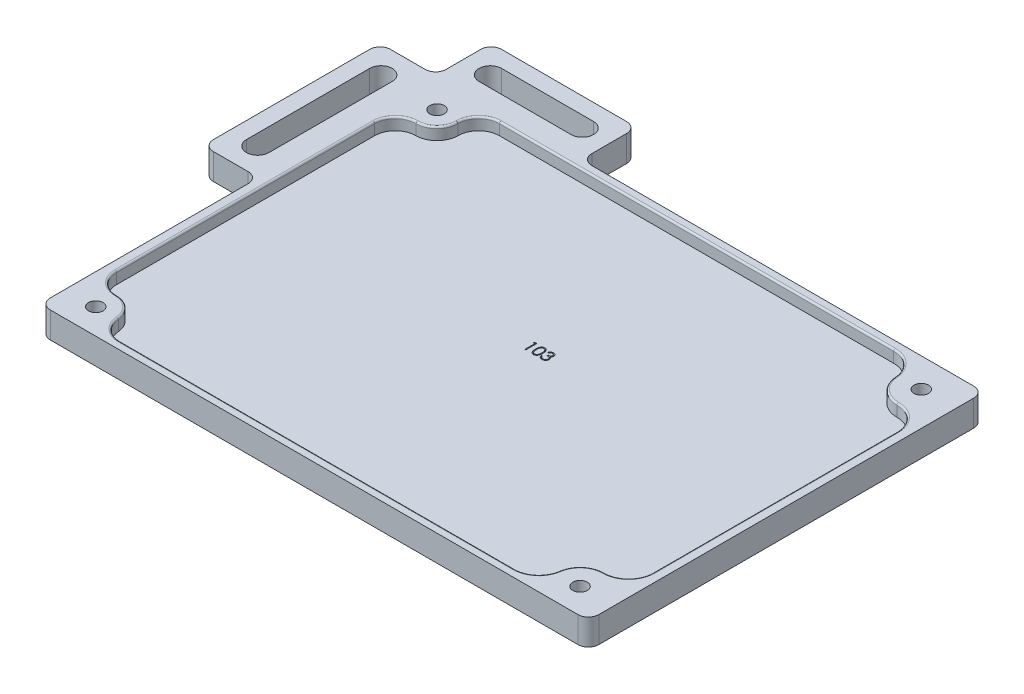
SolidWorks part; units mm, degrees
ref_plane "Front Plane" through (0, 0, 0) normal (0, 0, 1) x (1, 0, 0)
ref_plane "Top Plane" through (0, 0, 0) normal (0, 1, 0) x (1, 0, 0)
ref_plane "Right Plane" through (0, 0, 0) normal (1, 0, 0) x (0, 0, -1)
sketch "Sketch1" plane through (0, 0, 0) normal (0, 1, 0) x (1, 0, 0)
  line L1 (0, 0) -> (158, 0)
  line L2 (0, 0) -> (0, 114)
  line L3 (0, 114) -> (158, 114)
  line L4 (158, 0) -> (158, 114)
  line L5 (2.75, 2.35) -> (155.25, 2.35) construction
  line L6 (2.75, 2.35) -> (2.75, 111.65) construction
  line L7 (2.75, 111.65) -> (155.25, 111.65) construction
  line L8 (155.25, 2.35) -> (155.25, 111.65) construction
  circle A0 centre (8.75, 105.65) radius 2.09
  circle A1 centre (8.75, 7.35) radius 2.09
  circle A2 centre (148.25, 7.35) radius 2.09
  circle A3 centre (148.25, 105.65) radius 2.09
  point P20 (78.7625, 58.0063)
  dimension "D3" = 4.18
  dimension "D1" = 158
  dimension "D2" = 114
  dimension "D4" = 7
  dimension "D5" = 152.5
  dimension "D6" = 109.3
  dimension "D7" = 2.75
  dimension "D8" = 2.35
  dimension "D9" = 6
  dimension "D10" = 5
  dimension "D11" = 6
extrude "Boss-Extrude1" add sketch "Sketch1" along normal blind 7.5
extrude "Boss-Extrude2" add sketch "Sketch1<2>" along normal blind 2 from surface contours A0 | A3 | A1 | A2 region at (8.75, 0, -105.65) region at (148.25, 0, -105.65) starting at face at (148.25, 0, -5.26)
sketch "Sketch1<2>" plane through (0, 0, 0) normal (0, 1, 0) x (1, 0, 0) same geometry as "Sketch1"
sketch "Sketch2" plane through (0, 7.5, 0) normal (0, 1, 0) x (1, 0, 0)
  line L1 (20.7083, 2.35) -> (134.3936, 2.35)
  line L2 (2.75, 19.35) -> (2.75, 93.65)
  line L3 (20.75, 111.65) -> (134.2858, 111.65)
  line L4 (155.25, 21.35) -> (155.25, 91.65)
  arc A0 (8.75, 99.65) -> (14.75, 105.65) centre (8.75, 105.65) ccw
  arc A1 (14.7291, 7.85) -> (8.75, 13.35) centre (8.75, 7.35) ccw
  arc A2 (148.25, 14.35) -> (141.3218, 8.35) centre (148.25, 7.35) ccw
  arc A3 (141.2679, 105.15) -> (148.25, 98.65) centre (148.25, 105.65) ccw
  arc A4 (8.75, 99.65) -> (2.75, 93.65) centre (8.75, 93.65) ccw
  arc A5 (14.75, 105.65) -> (20.75, 111.65) centre (20.75, 105.65) cw
  arc A6 (8.75, 13.35) -> (2.75, 19.35) centre (8.75, 19.35) cw
  arc A7 (20.7083, 2.35) -> (14.7291, 7.85) centre (20.7083, 8.35) cw
  arc A8 (148.25, 14.35) -> (155.25, 21.35) centre (148.25, 21.35) ccw
  arc A9 (141.3218, 8.35) -> (134.3936, 2.35) centre (134.3936, 9.35) cw
  arc A10 (141.2679, 105.15) -> (134.2858, 111.65) centre (134.2858, 104.65) ccw
  arc A11 (148.25, 98.65) -> (155.25, 91.65) centre (148.25, 91.65) cw
  dimension "D1" = 6
  dimension "D2" = 6
  dimension "D3" = 6
  dimension "D4" = 7
  dimension "D5" = 7
  dimension "D6" = 7
extrude "Cut-Extrude1" cut sketch "Sketch2" against normal blind 3.5
sketch "Sketch3" plane through (0, 7.5, 0) normal (0, 1, 0) x (1, 0, 0)
  line L0 (-8, 70.75) -> (-8, 106.25) construction
  line L1 (0, 114) -> (-16, 114)
  line L2 (0, 114) -> (0, 63)
  line L3 (0, 63) -> (-16, 63)
  line L4 (-16, 114) -> (-16, 63)
  line L5 (-11.25, 70.75) -> (-11.25, 106.25)
  line L6 (-4.75, 70.75) -> (-4.75, 106.25)
  line L7 (7.75, 122) -> (34.25, 122) construction
  line L8 (0, 114) -> (42, 114)
  line L9 (0, 114) -> (0, 130)
  line L10 (0, 130) -> (42, 130)
  line L11 (42, 114) -> (42, 130)
  line L12 (7.75, 125.25) -> (34.25, 125.25)
  line L13 (7.75, 118.75) -> (34.25, 118.75)
  arc A0 (-11.25, 70.75) -> (-4.75, 70.75) centre (-8, 70.75) ccw
  arc A1 (-4.75, 106.25) -> (-11.25, 106.25) centre (-8, 106.25) ccw
  arc A2 (7.75, 125.25) -> (7.75, 118.75) centre (7.75, 122) ccw
  arc A3 (34.25, 118.75) -> (34.25, 125.25) centre (34.25, 122) ccw
  point P7 (-8, 88.5)
  point P17 (21, 122)
  point P22 (-8, 109.5)
  point P23 (-8, 67.5)
  point P24 (4.5, 122)
  point P25 (37.5, 122)
  line M35 (0, 114) -> (0, 0)
  line M38 (158, 114) -> (0, 114)
  dimension "D1" = 51
  dimension "D2" = 16
  dimension "D3" = 8
  dimension "D4" = 6.5
  dimension "D5" = 4.5
  dimension "D6" = 4.5
  dimension "D7" = 16
  dimension "D8" = 42
  dimension "D9" = 8
  dimension "D10" = 4.5
  dimension "D11" = 4.5
  dimension "D12" = 6.5
extrude "Boss-Extrude3" add sketch "Sketch3" against normal up to surface (7.5 mm away) contours L11 L10 L9 A3 L13 A2 L12 M38 | L1 L4 L3 A1 L6 A0 L5 M35 region at (-0.5345, 7.5, -88.5) region at (0.4494, 7.5, -122) up to face at (79, 0, -57)
fillet "Fillet1" radius 0.5 16 edges at (139.0555, 7.5, -109.7735) (143.4803, 7.5, -100.5265) (153.1997, 7.5, -96.5997) (155.25, 7.5, -56.5) (153.1997, 7.5, -16.4003) (143.6674, 7.5, -12.6415) (138.9762, 7.5, -4.0585) (77.5509, 7.5, -2.35) (16.6462, 7.5, -3.9341) (12.812, 7.5, -11.7659) (4.5074, 7.5, -15.1074) (2.75, 7.5, -56.5) (4.5074, 7.5, -97.8926) (12.9926, 7.5, -101.4074) (16.5074, 7.5, -109.8926) (77.5179, 7.5, -111.65)
fillet "Fillet2" radius 3 10 edges at (-16, 3.75, -63) (0, 3.75, -63) (-16, 3.75, -114) (0, 3.75, -114) (0, 3.75, -130) (42, 3.75, -130) (42, 3.75, -114) (158, 3.75, -114) (158, 3.75, 0) (0, 3.75, 0)
sketch "Sketch4" plane through (0, 4, 0) normal (0, 1, 0) x (1, 0, 0)
  text T0 "103"
extrude "Cut-Extrude2" cut sketch "Sketch4" against normal blind 1
